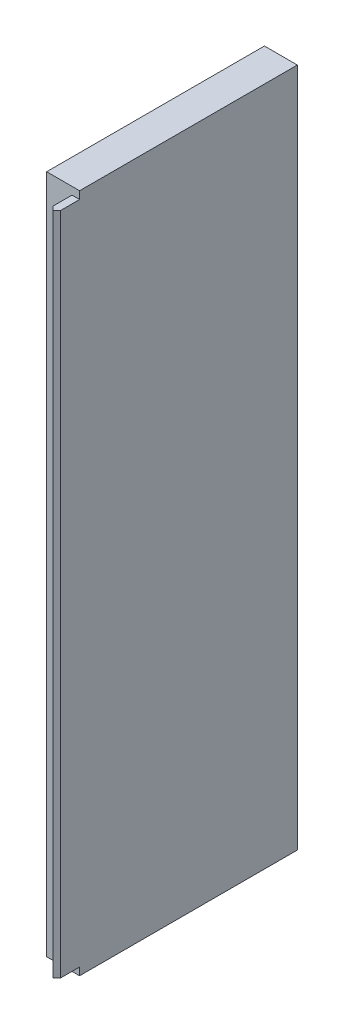
SolidWorks part; units mm, degrees
ref_plane "Front Plane" through (0, 0, 0) normal (0, 0, 1) x (1, 0, 0)
ref_plane "Top Plane" through (0, 0, 0) normal (0, 1, 0) x (1, 0, 0)
ref_plane "Right Plane" through (0, 0, 0) normal (1, 0, 0) x (0, 0, -1)
sketch "Sketch1" plane through (0, 0, 0) normal (0, 1, 0) x (1, 0, 0)
  line L0 (0, -16) -> (0, 16)
  line L1 (0, 16) -> (-4, 16)
  line L2 (-4, 16) -> (-4, 17.2)
  line L3 (-4, 17.2) -> (1.2, 17.2)
  line L4 (1.2, 17.2) -> (1.2, -17.2)
  line L5 (0, -17.2) -> (-4, -17.2)
  line L6 (-4, -17.2) -> (-4, -16)
  line L7 (-4, -16) -> (0, -16)
  line L8 (1.2, -17.2) -> (1.2, -21.2)
  line L9 (1.2, -21.2) -> (0, -21.2)
  line L10 (0, -21.2) -> (0, -17.2)
  point P4 (0, 0)
  dimension "D1" = 32
  dimension "D2" = 1.2
  dimension "D3" = 4
  dimension "D4" = 1.2
  dimension "D5" = 4
extrude "Boss-Extrude1" add sketch "Sketch1" along normal blind 105
sketch "Sketch2" plane through (0, 105, 0) normal (0, 1, 0) x (1, 0, 0)
  line L1 (1.2, 17.2) -> (-4, 17.2)
  line L2 (1.2, 17.2) -> (1.2, -17.2)
  line L3 (1.2, -17.2) -> (-4, -17.2)
  line L4 (-4, 17.2) -> (-4, -17.2)
extrude "Boss-Extrude2" add sketch "Sketch2" along normal blind 1.2
sketch "Sketch3" plane through (0, 0, 0) normal (0, -1, 0) x (1, 0, 0)
  line L1 (1.2, -17.2) -> (-4, -17.2)
  line L2 (1.2, -17.2) -> (1.2, 17.2)
  line L3 (1.2, 17.2) -> (-4, 17.2)
  line L4 (-4, -17.2) -> (-4, 17.2)
extrude "Boss-Extrude3" add sketch "Sketch3" along normal blind 1.2
sketch "Sketch4" plane through (0, 0, 0) normal (0, 1, 0) x (1, 0, 0)
  line L0 (0, 16) -> (0, -16) construction
  line L1 (0, -12.5) -> (-3, -12.5)
  line L2 (0, -12.5) -> (0, -9.5)
  line L3 (0, -9.5) -> (-3, -9.5)
  line L4 (-3, -12.5) -> (-3, -9.5)
  line L5 (0, -9.5) -> (0, -5.1667) construction
  line L6 (0, -5.1667) -> (-3, -5.1667)
  line L7 (0, -5.1667) -> (0, -2.1667)
  line L8 (0, -2.1667) -> (-3, -2.1667)
  line L9 (-3, -5.1667) -> (-3, -2.1667)
  line L10 (0, 2.1667) -> (-3, 2.1667)
  line L11 (0, 2.1667) -> (0, 5.1667)
  line L12 (0, 5.1667) -> (-3, 5.1667)
  line L13 (-3, 2.1667) -> (-3, 5.1667)
  line L14 (0, 9.5) -> (-3, 9.5)
  line L15 (0, 9.5) -> (0, 12.5)
  line L16 (0, 12.5) -> (-3, 12.5)
  line L17 (-3, 9.5) -> (-3, 12.5)
  line L18 (0, -2.1667) -> (0, 2.1667) construction
  line L19 (0, 5.1667) -> (0, 9.5) construction
  line L20 (-4, -16) -> (-4, 16) construction
  point P18 (0, 0)
  dimension "D1" = 3
  dimension "D2" = 22
  dimension "D3" = 1
extrude "Cut-Extrude1" cut sketch "Sketch4" against normal up to next
chamfer "Chamfer1" distance 1 angle 45 2 edges at (0, 52.5, 21.2) (1.2, 52.5, 21.2)
